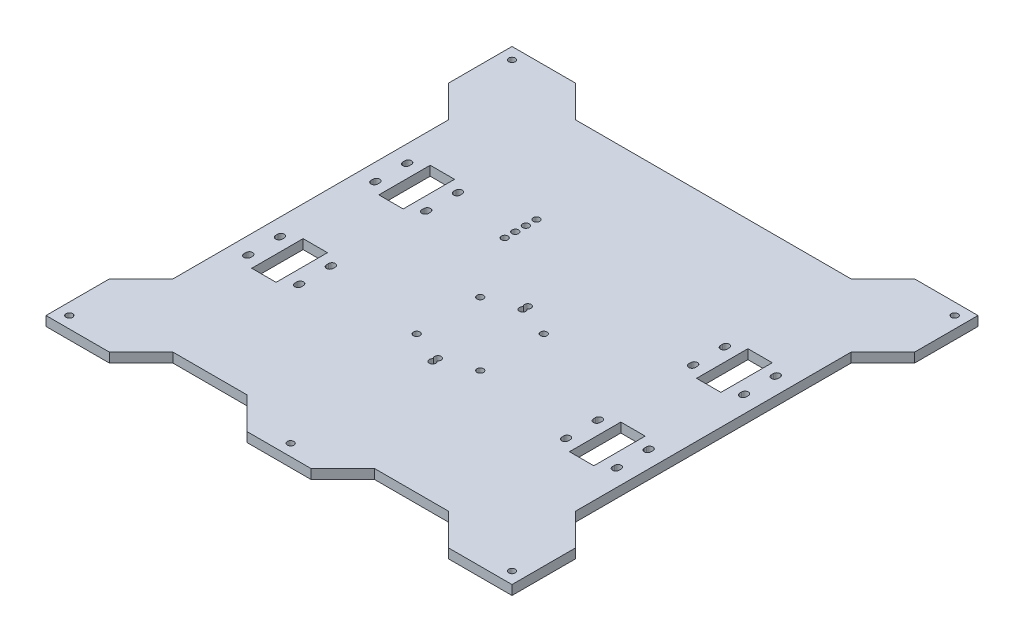
SolidWorks part; units mm, degrees
ref_plane "Front Plane" through (0, 0, 0) normal (0, 0, 1) x (1, 0, 0)
ref_plane "Top Plane" through (0, 0, 0) normal (0, 1, 0) x (1, 0, 0)
ref_plane "Right Plane" through (0, 0, 0) normal (1, 0, 0) x (0, 0, -1)
sketch "Sketch1" plane through (0, 0, 0) normal (0, 1, 0) x (1, 0, 0)
  line L1 (-110, 110) -> (110, 110)
  line L2 (-110, 110) -> (-110, -110)
  line L3 (-110, -110) -> (110, -110)
  line L4 (110, 110) -> (110, -110)
  line L5 (-110, 110) -> (110, -110) construction
  line L6 (-110, -110) -> (110, 110) construction
  point P0 (0, 0)
  dimension "D1" = 220
  dimension "D2" = 220
extrude "Square" add sketch "Sketch1" along normal blind 4.5
sketch "Sketch2" plane through (0, 4.5, 0) normal (0, 1, 0) x (1, 0, 0)
  line L0 (0, 110) -> (0, -110) construction
  line L1 (110, 110) -> (-110, 110) construction
  line L2 (-110, -110) -> (110, -110) construction
  line L3 (-110, 0) -> (110, 0) construction
  line L4 (-110, 110) -> (-110, -110) construction
  line L5 (110, -110) -> (110, 110) construction
  line L6 (75, 110) -> (75, -110) construction
  line L7 (75, 30) -> (0, 30) construction
  line L8 (75, -30) -> (0, -30) construction
  circle A0 centre (87, 38) radius 1.55
  circle A1 centre (87, 22) radius 1.55
  circle A2 centre (63, 22) radius 1.55
  circle A3 centre (63, 38) radius 1.55
  circle A4 centre (-63, 38) radius 1.55
  circle A5 centre (-63, 22) radius 1.55
  circle A6 centre (-87, 22) radius 1.55
  circle A7 centre (-87, 38) radius 1.55
  circle A8 centre (-87, 22) radius 1.55
  circle A9 centre (-87, 38) radius 1.55
  circle A10 centre (-63, 38) radius 1.55
  circle A11 centre (-63, 22) radius 1.55
  circle A12 centre (63, 22) radius 1.55
  circle A13 centre (63, 38) radius 1.55
  circle A14 centre (87, 38) radius 1.55
  circle A15 centre (87, 22) radius 1.55
  circle A16 centre (87, -22) radius 1.55
  circle A17 centre (87, -38) radius 1.55
  circle A18 centre (63, -38) radius 1.55
  circle A19 centre (63, -22) radius 1.55
  circle A20 centre (-63, -22) radius 1.55
  circle A21 centre (-63, -38) radius 1.55
  circle A22 centre (-87, -38) radius 1.55
  circle A23 centre (-87, -22) radius 1.55
  circle A24 centre (-87, -38) radius 1.55
  circle A25 centre (-87, -22) radius 1.55
  circle A26 centre (-63, -22) radius 1.55
  circle A27 centre (-63, -38) radius 1.55
  circle A28 centre (63, -38) radius 1.55
  circle A29 centre (63, -22) radius 1.55
  circle A30 centre (87, -22) radius 1.55
  circle A31 centre (87, -38) radius 1.55
  dimension "D6" = 3.1
  dimension "D7" = 3.1
  dimension "D1" = 75
  dimension "D2" = 30
  dimension "D3" = 16
  dimension "D5" = 12
extrude "LM8UU-Holders" cut sketch "Sketch2" against normal through all contours A7 | A6 | A5 | A4 | A20 | A21 | A22 | A23 | A19 | A18 | A17 | A16 | A1 | A0 | A3 | A2 region at (87, 4.5, -38) region at (87, 4.5, -22) region at (63, 4.5, -22) region at (63, 4.5, -38) region at (-63, 4.5, -38) region at (-63, 4.5, -22) region at (-87, 4.5, -22) region at (-87, 4.5, -38) region at (87, 4.5, 22) region at (87, 4.5, 38) region at (63, 4.5, 38) region at (63, 4.5, 22) region at (-63, 4.5, 22) region at (-63, 4.5, 38) region at (-87, 4.5, 38) region at (-87, 4.5, 22)
sketch "Sketch10" plane through (0, 4.5, 0) normal (0, 1, 0) x (1, 0, 0)
  line L0 (0, 110) -> (0, -79.9796) construction
  line L3 (-26.5242, 0) -> (110, 0) construction
  line L6 (75, 110) -> (75, -110) construction
  line L7 (75, 30) -> (-75, 30) construction
  line L8 (87, 22) -> (87, 23) construction
  line L9 (110, 110) -> (-110, 110) construction
  line L10 (110, -110) -> (110, 110) construction
  line L11 (85.45, 22) -> (85.45, 23)
  line L12 (88.55, 22) -> (88.55, 23)
  line L13 (87, 38) -> (87, 37) construction
  line L14 (88.55, 38) -> (88.55, 37)
  line L15 (85.45, 38) -> (85.45, 37)
  line L16 (63, 38) -> (63, 37) construction
  line L17 (61.45, 38) -> (61.45, 37)
  line L18 (64.55, 38) -> (64.55, 37)
  line L19 (63, 22) -> (63, 23) construction
  line L20 (64.55, 22) -> (64.55, 23)
  line L21 (61.45, 22) -> (61.45, 23)
  line L22 (75, -30) -> (-75, -30) construction
  line L23 (87, -22) -> (87, -23) construction
  line L24 (85.45, -22) -> (85.45, -23)
  line L25 (88.55, -22) -> (88.55, -23)
  line L26 (87, -38) -> (87, -37) construction
  line L27 (88.55, -38) -> (88.55, -37)
  line L28 (85.45, -38) -> (85.45, -37)
  line L29 (63, -38) -> (63, -37) construction
  line L30 (61.45, -38) -> (61.45, -37)
  line L31 (64.55, -38) -> (64.55, -37)
  line L32 (63, -22) -> (63, -23) construction
  line L33 (64.55, -22) -> (64.55, -23)
  line L34 (61.45, -22) -> (61.45, -23)
  line L35 (26.5242, 0) -> (-110, 0) construction
  line L36 (-87, 22) -> (-87, 23) construction
  line L37 (-85.45, 22) -> (-85.45, 23)
  line L38 (-88.55, 22) -> (-88.55, 23)
  line L39 (-87, 38) -> (-87, 37) construction
  line L40 (-88.55, 38) -> (-88.55, 37)
  line L41 (-85.45, 38) -> (-85.45, 37)
  line L42 (-63, 38) -> (-63, 37) construction
  line L43 (-61.45, 38) -> (-61.45, 37)
  line L44 (-64.55, 38) -> (-64.55, 37)
  line L45 (-63, 22) -> (-63, 23) construction
  line L46 (-64.55, 22) -> (-64.55, 23)
  line L47 (-61.45, 22) -> (-61.45, 23)
  line L48 (-87, -22) -> (-87, -23) construction
  line L49 (-85.45, -22) -> (-85.45, -23)
  line L50 (-88.55, -22) -> (-88.55, -23)
  line L51 (-87, -38) -> (-87, -37) construction
  line L52 (-88.55, -38) -> (-88.55, -37)
  line L53 (-85.45, -38) -> (-85.45, -37)
  line L54 (-63, -38) -> (-63, -37) construction
  line L55 (-61.45, -38) -> (-61.45, -37)
  line L56 (-64.55, -38) -> (-64.55, -37)
  line L57 (-63, -22) -> (-63, -23) construction
  line L58 (-64.55, -22) -> (-64.55, -23)
  line L59 (-61.45, -22) -> (-61.45, -23)
  arc A0 (61.45, 38) -> (64.55, 38) centre (63, 38) cw
  arc A1 (88.55, 38) -> (85.45, 38) centre (87, 38) ccw
  arc A2 (85.45, 22) -> (88.55, 22) centre (87, 22) ccw
  arc A3 (88.55, 23) -> (85.45, 23) centre (87, 23) ccw
  arc A4 (85.45, 37) -> (88.55, 37) centre (87, 37) ccw
  arc A5 (64.55, 37) -> (61.45, 37) centre (63, 37) cw
  arc A6 (64.55, 22) -> (61.45, 22) centre (63, 22) cw
  arc A7 (61.45, 23) -> (64.55, 23) centre (63, 23) cw
  arc A8 (85.45, -22) -> (88.55, -22) centre (87, -22) cw
  arc A9 (88.55, -23) -> (85.45, -23) centre (87, -23) cw
  arc A10 (88.55, -38) -> (85.45, -38) centre (87, -38) cw
  arc A11 (85.45, -37) -> (88.55, -37) centre (87, -37) cw
  arc A12 (61.45, -38) -> (64.55, -38) centre (63, -38) ccw
  arc A13 (64.55, -37) -> (61.45, -37) centre (63, -37) ccw
  arc A14 (64.55, -22) -> (61.45, -22) centre (63, -22) ccw
  arc A15 (61.45, -23) -> (64.55, -23) centre (63, -23) ccw
  arc A16 (-85.45, 22) -> (-88.55, 22) centre (-87, 22) cw
  arc A17 (-88.55, 23) -> (-85.45, 23) centre (-87, 23) cw
  arc A18 (-88.55, 38) -> (-85.45, 38) centre (-87, 38) cw
  arc A19 (-85.45, 37) -> (-88.55, 37) centre (-87, 37) cw
  arc A20 (-61.45, 38) -> (-64.55, 38) centre (-63, 38) ccw
  arc A21 (-64.55, 37) -> (-61.45, 37) centre (-63, 37) ccw
  arc A22 (-64.55, 22) -> (-61.45, 22) centre (-63, 22) ccw
  arc A23 (-61.45, 23) -> (-64.55, 23) centre (-63, 23) ccw
  arc A24 (-85.45, -22) -> (-88.55, -22) centre (-87, -22) ccw
  arc A25 (-88.55, -23) -> (-85.45, -23) centre (-87, -23) ccw
  arc A26 (-88.55, -38) -> (-85.45, -38) centre (-87, -38) ccw
  arc A27 (-85.45, -37) -> (-88.55, -37) centre (-87, -37) ccw
  arc A28 (-61.45, -38) -> (-64.55, -38) centre (-63, -38) cw
  arc A29 (-64.55, -37) -> (-61.45, -37) centre (-63, -37) cw
  arc A30 (-64.55, -22) -> (-61.45, -22) centre (-63, -22) cw
  arc A31 (-61.45, -23) -> (-64.55, -23) centre (-63, -23) cw
  point P8 (87, 22.5)
  point P19 (87, 37.5)
  point P28 (63, 37.5)
  point P35 (63, 22.5)
  point P44 (87, -22.5)
  point P51 (87, -37.5)
  point P58 (63, -37.5)
  point P65 (63, -22.5)
  point P73 (0, 30)
  point P74 (0, -30)
  point P76 (-87, 22.5)
  point P83 (-87, 37.5)
  point P90 (-63, 37.5)
  point P97 (-63, 22.5)
  point P104 (-87, -22.5)
  point P111 (-87, -37.5)
  point P118 (-63, -37.5)
  point P125 (-63, -22.5)
  dimension "D1" = 75
  dimension "D2" = 30
  dimension "D3" = 16
  dimension "D5" = 12
  dimension "D4" = 1.55
  dimension "D7" = 1.55
  dimension "D8" = 1
  dimension "D9" = 1
sketch "Sketch3" plane through (0, 4.5, 0) normal (0, 1, 0) x (1, 0, 0)
  line L0 (0, -110) -> (0, 110) construction
  line L1 (-110, -110) -> (110, -110) construction
  line L2 (110, 110) -> (-110, 110) construction
  line L3 (110, -15) -> (-110, -15) construction
  line L6 (15, -30) -> (-15, -30) construction
  line L7 (15, 0) -> (-15, 0) construction
  line L8 (110, -110) -> (110, 110) construction
  line L9 (-110, 110) -> (-110, -110) construction
  line L10 (110, 0) -> (-110, 0) construction
  circle A0 centre (-15, -30) radius 1.55
  circle A1 centre (15, -30) radius 1.55
  circle A2 centre (15, 0) radius 1.55
  circle A3 centre (-15, 0) radius 1.55
  point P16 (0, -30)
  dimension "D1" = 3.1
  dimension "D2" = 15
  dimension "D3" = 15
  dimension "D5" = 15
extrude "DefaultBelt" cut sketch "Sketch3" against normal through all
sketch "Sketch4" plane through (0, 4.5, 0) normal (0, 1, 0) x (1, 0, 0)
  line L0 (0, 110) -> (0, -110) construction
  line L1 (110, 110) -> (-110, 110) construction
  line L2 (-110, -110) -> (110, -110) construction
  line L3 (-15, -1.55) -> (-15, -28.45) construction
  line L4 (15, -28.45) -> (15, -1.55) construction
  line L5 (15, -15) -> (-15, -15) construction
  arc A0 (-0.9165, 6.25) -> (0.9165, 6.25) centre (0, 5) ccw
  arc A1 (0.9165, 6.25) -> (-0.9165, 6.25) centre (0, 7.5) ccw
  arc A2 (0.9165, -36.25) -> (-0.9165, -36.25) centre (0, -37.5) cw
  arc A3 (-0.9165, -36.25) -> (0.9165, -36.25) centre (0, -35) cw
  circle A4 centre (-15, 0) radius 1.55 construction
  circle A5 centre (-15, -30) radius 1.55 construction
  circle A6 centre (15, -30) radius 1.55 construction
  circle A7 centre (15, 0) radius 1.55 construction
  dimension "D1" = 3.1
  dimension "D2" = 3.1
  dimension "D3" = 20
  dimension "D4" = 22.5
extrude "BeltOptions" cut sketch "Sketch4" against normal through all
sketch "Sketch5" plane through (0, 4.5, 0) normal (0, 1, 0) x (1, 0, 0)
  line L0 (-110, 0) -> (110, 0) construction
  line L1 (-110, 110) -> (-110, -110) construction
  line L2 (110, -110) -> (110, 110) construction
  line L3 (0, 110) -> (0, -110) construction
  line L4 (110, 110) -> (-110, 110) construction
  line L5 (-110, 110) -> (-110, 80)
  line L6 (-110, 80) -> (-95, 65)
  line L7 (-95, 65) -> (-95, -65)
  line L8 (0, 0) -> (-110, 110) construction
  line L9 (-65, 95) -> (65, 95)
  line L10 (-80, 110) -> (-65, 95)
  line L11 (-110, 110) -> (-80, 110)
  line L12 (-95, 65) -> (-95, -65)
  line L13 (0, 0) -> (110, 110) construction
  line L14 (95, 65) -> (95, -65)
  line L15 (110, 110) -> (80, 110)
  line L16 (80, 110) -> (65, 95)
  line L17 (95, 65) -> (95, -65)
  line L18 (110, 80) -> (95, 65)
  line L19 (110, 110) -> (110, 80)
  line L20 (0, 0) -> (110, -110) construction
  line L21 (0, 0) -> (-110, -110) construction
  line L22 (110, -110) -> (110, -80)
  line L23 (110, -80) -> (95, -65)
  line L24 (80, -110) -> (65, -95)
  line L25 (110, -110) -> (80, -110)
  line L26 (-110, -110) -> (-80, -110)
  line L27 (-80, -110) -> (-65, -95)
  line L28 (-65, -95) -> (65, -95)
  line L29 (-110, -80) -> (-95, -65)
  line L30 (-110, -110) -> (-110, -80)
  point P24 (0, 95)
  point P32 (95, 0)
  point P35 (-95, 0)
  point P36 (0, -95)
  circle M16 centre (15, -30) radius 1.55
  circle M18 centre (63, 38) radius 1.55
  circle M20 centre (87, 22) radius 1.55
  circle M22 centre (87, -38) radius 1.55
  circle M23 centre (63, -38) radius 1.55
  circle M24 centre (63, -22) radius 1.55
  circle M25 centre (-87, -22) radius 1.55
  circle M26 centre (-87, -38) radius 1.55
  circle M27 centre (-63, -38) radius 1.55
  circle M28 centre (-63, -22) radius 1.55
  circle M29 centre (-63, 38) radius 1.55
  circle M30 centre (-63, 22) radius 1.55
  circle M31 centre (-87, 22) radius 1.55
  circle M32 centre (-87, 38) radius 1.55
  line M33 (110, -110) -> (110, 110)
  line M34 (110, 110) -> (-110, 110)
  line M35 (-110, 110) -> (-110, -110)
  line M36 (-110, -110) -> (110, -110)
  dimension "D1" = 15
  dimension "D2" = 30
  dimension "D3" = 45
  dimension "D4" = 45
extrude "Shaping" cut sketch "Sketch5" against normal blind 10 flip side to cut contours L29 L27 L28 L24 L23 L14 L18 L16 L9 L10 L6 L7 M35 M36 M33 M34 M16 M18 M20 M22 M24 M26 M28 M30 M32 M31 M29 M27 M25 M23 region at (0.0423, 4.5, -0.013)
sketch "Sketch6" plane through (0, 4.5, 0) normal (0, 1, 0) x (1, 0, 0)
  line L0 (-110, 110) -> (110, -110) construction
  line L1 (-110, -110) -> (110, 110) construction
  line L2 (110, 80) -> (110, 110) construction
  line L3 (0, 95) -> (0, -95) construction
  line L4 (-65, 95) -> (65, 95) construction
  line L5 (-65, -95) -> (65, -95) construction
  line L6 (-95, 0) -> (95, 0) construction
  line L7 (-95, 65) -> (-95, -65) construction
  line L8 (95, 65) -> (95, -65) construction
  circle A0 centre (-104.5, 104.5) radius 1.55
  circle A1 centre (104.5, 104.5) radius 1.55
  circle A2 centre (104.5, -104.5) radius 1.55
  circle A3 centre (-104.5, -104.5) radius 1.55
  dimension "D2" = 3.1
  dimension "D1" = 45
  dimension "D3" = 104.5
extrude "Cut-Extrude5" cut sketch "Sketch6" against normal through all
sketch "Sketch7" plane through (0, 4.5, 0) normal (0, 1, 0) x (1, 0, 0)
  line L0 (-87, 38) -> (-63, 22) construction
  line L1 (-63, 22) -> (-87, 22) construction
  line L2 (-87, 22) -> (-63, 38) construction
  line L3 (-63, 38) -> (-87, 38) construction
  line L4 (-95, 0) -> (95, 0) construction
  line L5 (-80.75, 42.125) -> (-69.25, 42.125)
  line L6 (-80.75, 42.125) -> (-80.75, 17.875)
  line L7 (-80.75, 17.875) -> (-69.25, 17.875)
  line L8 (-69.25, 42.125) -> (-69.25, 17.875)
  line L9 (-80.75, 42.125) -> (-69.25, 17.875) construction
  line L10 (-80.75, 17.875) -> (-69.25, 42.125) construction
  line L11 (-95, 65) -> (-95, -65) construction
  line L12 (95, 65) -> (95, -65) construction
  line L13 (0, -95) -> (0, 95) construction
  line L14 (-65, -95) -> (65, -95) construction
  line L15 (-65, 95) -> (65, 95) construction
  line L16 (-80.75, -17.875) -> (-69.25, -42.125) construction
  line L17 (-80.75, -42.125) -> (-69.25, -17.875) construction
  line L18 (-63, -38) -> (-87, -38) construction
  line L19 (-87, -22) -> (-63, -38) construction
  line L20 (-63, -22) -> (-87, -22) construction
  line L21 (-87, -38) -> (-63, -22) construction
  line L22 (-69.25, -42.125) -> (-69.25, -17.875)
  line L23 (-80.75, -17.875) -> (-69.25, -17.875)
  line L24 (-80.75, -42.125) -> (-80.75, -17.875)
  line L25 (-80.75, -42.125) -> (-69.25, -42.125)
  line L26 (-80.75, 17.875) -> (-69.25, 42.125) construction
  line L27 (80.75, 17.875) -> (69.25, 42.125) construction
  line L28 (87, -38) -> (63, -22) construction
  line L29 (63, -22) -> (87, -22) construction
  line L30 (87, -22) -> (63, -38) construction
  line L31 (63, -38) -> (87, -38) construction
  line L32 (80.75, -42.125) -> (69.25, -17.875) construction
  line L33 (80.75, -17.875) -> (69.25, -42.125) construction
  line L34 (80.75, 17.875) -> (69.25, 42.125) construction
  line L35 (80.75, 42.125) -> (69.25, 17.875) construction
  line L36 (63, 38) -> (87, 38) construction
  line L37 (87, 22) -> (63, 38) construction
  line L38 (63, 22) -> (87, 22) construction
  line L39 (87, 38) -> (63, 22) construction
  line L40 (80.75, -42.125) -> (69.25, -42.125)
  line L41 (80.75, -42.125) -> (80.75, -17.875)
  line L42 (80.75, -17.875) -> (69.25, -17.875)
  line L43 (69.25, -42.125) -> (69.25, -17.875)
  line L44 (69.25, 42.125) -> (69.25, 17.875)
  line L45 (80.75, 17.875) -> (69.25, 17.875)
  line L46 (80.75, 42.125) -> (80.75, 17.875)
  line L47 (80.75, 42.125) -> (69.25, 42.125)
  point P4 (-75, 30)
  point P33 (-75, -30)
  point P50 (75, -30)
  point P51 (75, 30)
  dimension "D1" = 11.5
  dimension "D2" = 24.25
extrude "Cut-Extrude6" cut sketch "Sketch7" against normal through all
sketch "Sketch8" plane through (0, 4.5, 0) normal (0, 1, 0) x (1, 0, 0)
  line L3 (-65, 95) -> (65, 95) construction
  line L4 (-33.45, 45) -> (-33.45, 30) construction
  circle A0 centre (-33.45, 45) radius 1.55
  circle A1 centre (-33.45, 40) radius 1.55
  circle A2 centre (-33.45, 35) radius 1.55
  circle A3 centre (-33.45, 30) radius 1.55
  dimension "D1" = 3.1
  dimension "D2" = 50
extrude "EndstopTrigger" cut sketch "Sketch8" against normal through all
pattern_linear "LPattern1" [suppressed] count 2 spacing 30 of bodies 108
sketch "Sketch9" plane through (0, 4.5, 0) normal (0, 1, 0) x (1, 0, 0)
  line L0 (-80, -110) -> (80, -110) construction
  line L1 (0, -110) -> (0, -95) construction
  line L2 (-65, -95) -> (65, -95) construction
  line L3 (15, -110) -> (-15, -110)
  line L4 (-15, -110) -> (-30, -95)
  line L5 (-30, -95) -> (30, -95)
  line L6 (-80, -110) -> (-65, -95) construction
  line L9 (15, -110) -> (30, -95)
  line L10 (-104.5, -104.5) -> (104.5, -104.5) construction
  circle A0 centre (0, -104.5) radius 1.55
  dimension "D2" = 15
  dimension "D3" = 3.1
  dimension "D1" = 90
extrude "Boss-Extrude1" add sketch "Sketch9" against normal through all
extrude "HolesToSlots" cut sketch "Sketch10" against normal through all
equation "\"X-ROD-SPACING\"=45"
equation "\"Y-ROD-SPACING\"=75"
equation "\"Z-ROD-SPACING\"=17.5"
equation "\"Y-BED-OFFSET\"=2"
equation "\"Y-BED-ROD-INSET\"=3.5"
equation "\"T-SLOT-NUT-FILLET-RADIUS\"=0.25"
equation "\"T-SLOT-SCREW-SHAFT-RADIUS\"=1.75"
equation "\"T-SLOT-SCREW-SHAFT-CUTOUT-LENGTH\"=10.5"
equation "\"T-SLOT-NUT-DEPTH\"=4.2"
equation "\"T-SLOT-NUT-WIDTH\"=3"
equation "\"T-SLOT-NUT-END-DISTANCE\"=8"
equation "\"ACRYLIC-THICKNESS\"=10"
equation "\"ACRYLIC-THICKNESS2\"=4.5"
equation "\"ACRYLIC-TAB-CUTOUT-SIZE\"=\"ACRYLIC-THICKNESS\"+\"ACRYLIC-TAB-TOLERANCE\"*2"
equation "\"ACRYLIC-TAB-WIDTH\"=\"ACRYLIC-THICKNESS\""
equation "\"ACRYLIC-M3-HOLE\"=3.1"
equation "\"SMOOTHROD-CAP-SCREW-DISTANCE\"=20"
equation "\"FRAME-WIDTH-INNER\"=370"
equation "\"NEMA17-HOLE-SPACING\"=31"
equation "\"NEMA17-CENTRAL-CUTOUT\"=22.5"
equation "\"Z-BRACKET-REACH\"=55"
equation "\"TOP-BRACKET-SPACING\"=40"
equation "\"SMOOTHROD-X-LENGTH\"=350"
equation "\"SMOOTHROD-Y-LENGTH\"=350"
equation "\"SMOOTHROD-Z-LENGTH\"=350"
equation "\"SMOOTHROD-TIGHTENING-HEADROOM\"=.25"
equation "\"LEADSCREW-Z-LENGTH\"=300"
equation "\"SCREW-LENGTH-FRAME\"=\"ACRYLIC-THICKNESS\" + 10"
equation "\"SCREW-HEAD-RADIUS\"=6"
equation "\"PRINTED-X-SMOOTHROD-DIAMETER\"=8.2"
equation "\"PRINTED-X-SMOOTHROD-CUTOUT\"=10"
equation "\"PRINTED-X-BASE-HEIGHT\"=10"
equation "\"PRINTED-LM8UU-CUTOUT-SIZE\"=15.25"
equation "\"PRINTED-LM8UU-CUTOUT-LENGTH\"=24.5"
equation "\"PRINTED-X-IDLER-HEIGHT\"=16"
equation "\"PSU-MOUNTING-WIDTH\"=95"
equation "\"PSU-MOUNTING-HEIGHT\"=177"
equation "\"Y-BELT-TO-ROD-DISTANCE\"=20"
equation "\"D6@Sketch2\"=\"ACRYLIC-M3-HOLE\""
equation "\"D7@Sketch2\"=\"ACRYLIC-M3-HOLE\""
equation "\"D1@Sketch2\"=\"Y-ROD-SPACING\""
equation "\"D1@Sketch3\"=\"ACRYLIC-M3-HOLE\""
equation "\"D2@Sketch6\"=\"ACRYLIC-M3-HOLE\""
equation "\"Y-BED-SCREW-SPACING\"=209"
equation "\"Y-BED-SCREW-CUTOUT-SLOT-HEIGHT\"=2"
equation "\"ACRYLIC-TAB-TOLERANCE\"=.1"
equation "\"Z-ROD-INSET\"=16"
equation "\"SCREW-LENGTH-MOTOR\"=\"ACRYLIC-THICKNESS\" + 5"
equation "\"SCREW-LENGTH-EXTRUDER\"=28"
equation "\"PRINTED-M3-HOLE\"=3.5"
equation "\"SPOOL-HOLDER-ROD-SPACING\"=150"
equation "\"ACRYLIC-X-CARRIAGE-WIDTH\"=55"
equation "\"ACRYLIC-X-CARRIAGE-HEIGHT\"=75"
equation "\"ACRYLIC-X-CARRIAGE-LM8UU-CUTOUT-WIDTH\"=24.25"
equation "\"ACRYLIC-X-CARRIAGE-LM8UU-CUTOUT-HEIGHT\"=11.5"
equation "\"ACRYLIC-X-CARRIAGE-SCREW-SPACING-X\"=15"
equation "\"ACRYLIC-X-CARRIAGE-SCREW-SPACING-Y\"=33"
equation "\"ACRYLIC-X-CARRIAGE-CENTER-TAB-SPACING\"=14"
equation "\"ACRYLIC-X-CARRIAGE-EXTRUDER-OFFSET\"=26"
equation "\"ACRYLIC-X-CARRIAGE-EXTRUDER-ANGLE\"=90"
equation "\"ACRYLIC-X-CARRIAGE-EXTRUDER-SHELF-DEPTH\"=\"ACRYLIC-X-CARRIAGE-EXTRUDER-OFFSET\" + 28"
equation "\"ACRYLIC-X-CARRIAGE-EXTRUDER-BRACE-SPACING\"=23"
equation "\"ACRYLIC-X-CARRIAGE-EXTRUDER-BRACE-TAB-OFFSET\"=20"
equation "\"ACRYLIC-X-CARRIAGE-EXTRUDER-BRACE-HEIGHT\"=35"
equation "\"ACRYLIC-X-CARRIAGE-EXTRUDER-BRACE-SCREW-SPACING\"=22"
equation "\"ACRYLIC-X-CARRIAGE-DUAL-WIDTH-MULTIPLIER\"=1.65"
equation "\"ACRYLIC-X-CARRIAGE-DUAL-HOTEND-SPACING\"=42"
equation "\"ACRYLIC-X-CARRIAGE-DUAL-WIDTH\"=75"
equation "\"ACRYLIC-X-CARRIAGE-DUAL-HOTEND-SEPARATION\"=36"
equation "\"ACRYLIC-X-CARRIAGE-DUAL-MOUNT-PLATE-DEPTH\"=75"
equation "\"ACRYLIC-X-CARRIAGE-DUAL-MOUNT-BRACE-WIDTH\"=33"
equation "\"ACRYLIC-X-CARRIAGE-DUAL-MOUNT-SCREW-WIDTH\"=40"
equation "\"BLOWER-FAN-WIDTH\"=15"
equation "\"D1@Sketch7\"=\"ACRYLIC-X-CARRIAGE-LM8UU-CUTOUT-HEIGHT\""
equation "\"D2@Sketch7\"=\"ACRYLIC-X-CARRIAGE-LM8UU-CUTOUT-WIDTH\""
equation "\"D1@Sketch8\"=\"ACRYLIC-M3-HOLE\""
equation "\"D2@Sketch4\"=\"ACRYLIC-M3-HOLE\""
equation "\"D1@Sketch4\"=\"ACRYLIC-M3-HOLE\""
equation "\"D3@Sketch4\"=20"
equation "\"D3@Sketch9\"=\"ACRYLIC-M3-HOLE\""
equation "\"D4@Sketch10\"=\"ACRYLIC-M3-HOLE\"/2"
equation "\"D7@Sketch10\"=\"ACRYLIC-M3-HOLE\" / 2"
